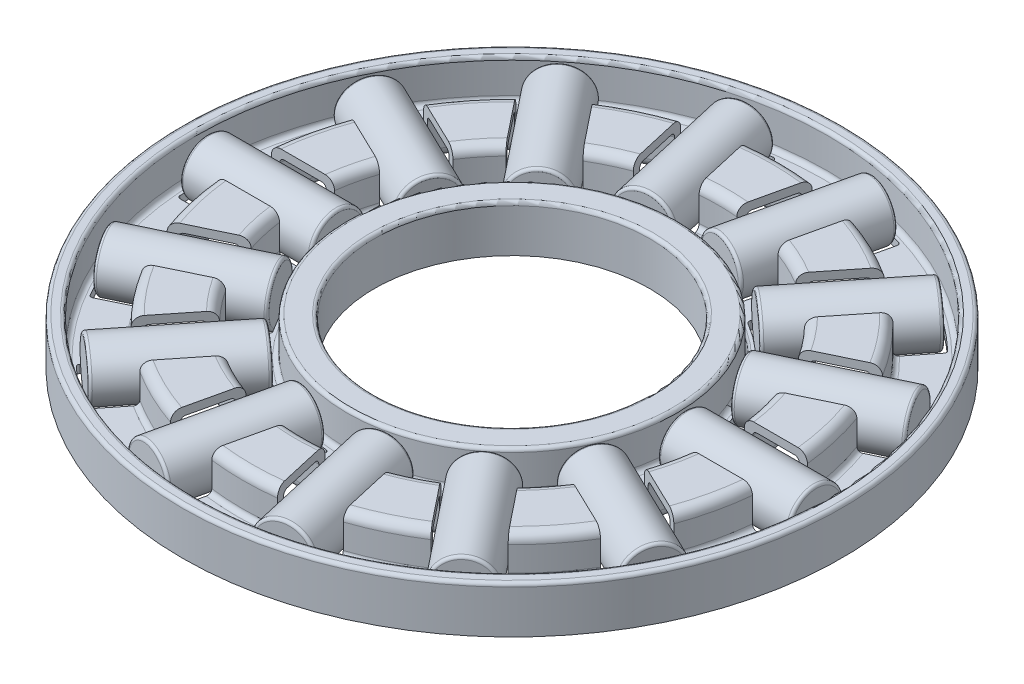
SolidWorks part; units mm, degrees
ref_plane "Front Plane" through (0, 0, 0) normal (0, 0, 1) x (1, 0, 0)
ref_plane "Top Plane" through (0, 0, 0) normal (0, 1, 0) x (1, 0, 0)
ref_plane "Right Plane" through (0, 0, 0) normal (1, 0, 0) x (0, 0, -1)
sketch "Sketch1" plane through (0, 0, 0) normal (1, 0, 0) x (0, 0, -1)
  line L0 (-12, 0) -> (12, 0) construction
  line L1 (-5.0125, 0) -> (5.0125, 0) construction
  line L2 (12, -1) -> (12, 1) construction
  line L3 (5.0125, -0.85) -> (5.0125, 0.85) construction
  line L4 (5.0125, -0.85) -> (5.3417, -0.85) construction
  line L5 (5.3417, -0.85) -> (5.3417, 0.5572) construction
  line L6 (5.3417, 0.5572) -> (5.6708, 0.5572) construction
  line L7 (5.6708, 0.5572) -> (5.6708, -0.85) construction
  line L8 (5.6708, -0.85) -> (7.8226, -0.85) construction
  line L9 (7.8226, -0.85) -> (7.8226, 0.5572) construction
  line L10 (7.8226, 0.5572) -> (9.5149, 0.5572) construction
  line L11 (9.5149, 0.5572) -> (9.5149, -0.85) construction
  line L12 (9.5149, -0.85) -> (11.6667, -0.85) construction
  line L13 (11.6667, -0.85) -> (11.6667, 0.5572) construction
  line L14 (11.6667, 0.5572) -> (11.8333, 0.5572) construction
  line L15 (5.0125, 0.85) -> (6, 0.85) construction
  line L16 (6, 0.85) -> (6, -0.5572) construction
  line L17 (6, -0.5572) -> (7.5298, -0.5572) construction
  line L18 (7.5298, -0.5572) -> (7.5298, 0.85) construction
  line L19 (7.5298, 0.85) -> (9.8077, 0.85) construction
  line L20 (9.8077, 0.85) -> (9.8077, -0.5572) construction
  line L21 (9.8077, -0.5572) -> (11.5, -0.5572) construction
  line L22 (11.5, -0.5572) -> (11.5, 0.85) construction
  line L23 (11.5, 0.85) -> (12, 0.85) construction
  line L24 (7.8226, 0.5572) -> (7.5298, 0.5572) construction
  line L25 (5.6708, 0.5572) -> (5.6708, 0.85) construction
  line L26 (9.5149, 0.5572) -> (9.8077, 0.5572) construction
  line L27 (6, -0.5572) -> (6, -0.85) construction
  line L28 (6, -0.5572) -> (5.6708, -0.5572) construction
  line L29 (11.6667, 0.5572) -> (11.5, 0.5572) construction
  line L30 (11.8333, 0.5572) -> (11.8333, -0.85) construction
  line L31 (11.8333, -0.85) -> (12, -0.85) construction
  line L32 (0, 1) -> (0, -1) construction
  line L33 (-6, 1) -> (6, 1) construction
  line L34 (-11.5, 0.85) -> (11.5, 0.85) construction
  line L35 (11.8333, 0.5572) -> (12, 0.5572) construction
  line L36 (7.5298, -0.5572) -> (7.5298, -0.85) construction
  line L37 (9.5149, 0.5572) -> (9.5149, 0.85) construction
  line L38 (5.3417, -0.5572) -> (5.0125, -0.5572) construction
  line L39 (5.6708, -0.5572) -> (5.3417, -0.5572) construction
  point P4 (0, 0)
  point P8 (0, 0)
  point P11 (12, 0)
  point P14 (5.0125, 0)
  point P45 (0, 1)
  point P48 (0, 0)
  point P49 (0, 1)
  point P55 (0, 0.85)
  dimension "OD" = 24
  dimension "ID" = 10.025
  dimension "Thickness" = 2
  dimension "Approx. Raceway Thickness" = 1.7
  dimension "Inner Raceway" = 12
  dimension "Outer Raceway" = 23
  dimension "Approx. Raceway Notch Width" = 1.6923
  dimension "D3" = 1.6923
sketch "Sketch2" plane through (0, 0, 0) normal (0, 1, 0) x (1, 0, 0)
  line L0 (6, 0) -> (11.5, 0) construction
  line L1 (11.225, 0) -> (6.275, 0)
  line L2 (11.1804, -1) -> (6.1948, -1)
  line L3 (11.1804, 1) -> (6.1948, 1)
  circle A0 centre (0, 0) radius 5.0125
  circle A1 centre (0, 0) radius 6
  circle A2 centre (0, 0) radius 11.5
  circle A3 centre (0, 0) radius 12
  arc A4 (6.1948, -1) -> (6.1948, 1) centre (0, 0) ccw
  arc A5 (11.1804, -1) -> (11.1804, 1) centre (0, 0) ccw
  arc A6 (11.1804, 1) -> (10.8767, 2.7747) centre (0, 0) ccw
  point P15 (8.75, 0)
  dimension "Approx. Roller Length" = 4.95
  dimension "Roller Thickness" = 2
  dimension "Roller Arc Length" = 2.0027
  dimension "Approx. Roller Gap" = 1.8024
sketch "Sketch3" plane through (0, 0, 0) normal (1, 0, 0) x (0, 0, -1)
  line L0 (5.3417, -0.85) -> (5.3417, 0.5572)
  line L1 (5.3417, 0.5572) -> (5.6708, 0.5572)
  line L2 (5.6708, 0.5572) -> (5.6708, -0.85)
  line L3 (5.6708, -0.85) -> (7.8226, -0.85)
  line L4 (7.8226, -0.85) -> (7.8226, 0.5572)
  line L5 (7.8226, 0.5572) -> (9.5149, 0.5572)
  line L6 (9.5149, 0.5572) -> (9.5149, -0.85)
  line L7 (9.5149, -0.85) -> (11.6667, -0.85)
  line L8 (11.6667, -0.85) -> (11.6667, 0.5572)
  line L9 (11.6667, 0.5572) -> (11.8333, 0.5572)
  line L10 (11.8333, 0.5572) -> (11.8333, -0.85)
  line L11 (11.8333, -0.85) -> (12, -0.85)
  line L12 (12, -0.85) -> (12, 0.85)
  line L13 (12, 0.85) -> (11.5, 0.85)
  line L14 (11.5, 0.85) -> (11.5, -0.5572)
  line L15 (11.5, -0.5572) -> (9.8077, -0.5572)
  line L16 (9.8077, -0.5572) -> (9.8077, 0.85)
  line L17 (9.8077, 0.85) -> (7.5298, 0.85)
  line L18 (7.5298, 0.85) -> (7.5298, -0.5572)
  line L19 (7.5298, -0.5572) -> (6, -0.5572)
  line L20 (6, -0.5572) -> (6, 0.85)
  line L21 (6, 0.85) -> (5.0125, 0.85)
  line L22 (5.0125, 0.85) -> (5.0125, -0.85)
  line L23 (5.0125, -0.85) -> (5.3417, -0.85)
revolve "Revolve1" add sketch "Sketch3" angle 360 about L32
fillet "Fillet1" radius 0.3385 4 edges at (0, -0.85, 9.5149) (0, -0.85, 11.6667) (0, -0.85, 5.6708) (0, -0.85, 7.8226)
fillet "Fillet2" radius 0.3385 2 edges at (0, 0.85, 9.8077) (0, 0.85, 7.5298)
fillet "Fillet3" radius 0.125 4 edges at (0, 0.85, 11.5) (0, 0.85, 12) (0, 0.85, 6) (0, 0.85, 5.0125)
fillet "Fillet4" radius 0.1692 6 edges at (0, 0.5572, 7.8226) (0, 0.5572, 9.5149) (0, -0.5572, 11.5) (0, -0.5572, 9.8077) (0, -0.5572, 7.5298) (0, -0.5572, 6)
sketch "Sketch4" plane through (0, 0, 0) normal (0, 1, 0) x (1, 0, 0)
  line L0 (6.1948, 1) -> (11.1804, 1)
  line L1 (6.1948, -1) -> (11.1804, -1)
  arc A0 (6.1948, -1) -> (6.1948, 1) centre (0, 0) ccw construction
  arc A1 (6.1948, -1) -> (6.1948, 1) centre (0, 0) ccw
  arc A2 (11.1804, -1) -> (11.1804, 1) centre (0, 0) ccw construction
  arc A3 (11.1804, -1) -> (11.1804, 1) centre (0, 0) ccw
extrude "Cut-Extrude1" cut sketch "Sketch4" against normal through all both and the other way through all
fillet "Fillet5" radius 0.1001 4 edges at (11.1804, -0.7036, -1) (11.1804, -0.7036, 1) (6.1948, -0.7036, -1) (6.1948, -0.7036, 1)
pattern_circular "CirPattern1" count 14 over 360 about axis through (0, 1, 0) along (0, -1, 0) of "Cut-Extrude1", "Fillet5"
sketch "Sketch5" plane through (0, 0, 0) normal (0, 1, 0) x (1, 0, 0)
  line L0 (6.3113, 0) -> (6.3113, 1)
  line L2 (6.3113, 1) -> (11.0884, 1)
  line L3 (11.0884, 1) -> (11.0884, 0)
  line L4 (11.0884, 0) -> (6.3113, 0)
  line L5 (11.225, 0) -> (6.275, 0) construction
revolve "Revolve2" add sketch "Sketch5" angle 360 about L1
fillet "Fillet6" radius 0.1001 2 edges at (6.3113, 0, -1) (11.0884, 0, -1)
pattern_circular "CirPattern2" count 14 over 360 about axis through (0, 1, 0) along (0, -1, 0) of bodies 107
ref_axis "Center Axis 1" through (0, 1.65, 0) along (0, -1, 0)
ref_plane "Contact Plane 1" through (0, 1, 0) normal (0, 1, 0) x (1, 0, 0)
ref_plane "Contact Plane 2" through (0, -1, 0) normal (0, 1, 0) x (1, 0, 0)
equation "\"Approx. Raceway Thickness@Sketch1\" = \"Thickness@Sketch1\" * .85"
equation "\"Approx. Raceway Notch Width@Sketch1\" =  ( \"Outer Raceway@Sketch1\" - \"Inner Raceway@Sketch1\" )  / 6.5"
equation "\"D3@Sketch1\" = \"Approx. Raceway Notch Width@Sketch1\""
equation "\"D1@Fillet2\"=\"D1@Fillet1\""
equation "\"D1@Fillet3\"=(\"OD@Sketch1\"-\"Outer Raceway@Sketch1\")/8"
equation "\"D1@Fillet1\" = \"Approx. Raceway Notch Width@Sketch1\" * 2 / 10"
equation "\"D1@Fillet4\"=\"D1@Fillet2\"/2"
equation "\"Approx. Roller Length@Sketch2\" =  ( \"Outer Raceway@Sketch1\" - \"Inner Raceway@Sketch1\" )  / 2 * .9"
equation "\"Approx. Roller Gap@Sketch2\" = \"Roller Arc Length@Sketch2\" * .9"
equation "\"Raceway Diff\"= ( \"Outer Raceway@Sketch1\" - \"Inner Raceway@Sketch1\" )"
equation "\"Circumference\"= ( \"Inner Raceway@Sketch1\" + ( \"Raceway Diff\" / 2 ) ) * 3.14"
equation "\"Instances\"= int ( \"Circumference\" /  ( \"Roller Arc Length@Sketch2\" + \"Approx. Roller Gap@Sketch2\" )  ) "
equation "\"D1@CirPattern1\"=\"Instances\""
equation "\"D1@Fillet5\" = \"Roller Arc Length@Sketch2\" / 20"
equation "\"D1@Fillet6\" = \"Roller Arc Length@Sketch2\" / 20"
equation "\"D1@CirPattern2\" = \"D1@CirPattern1\""
equation "\"Roller Thickness@Sketch2\" = \"Thickness@Sketch1\""
